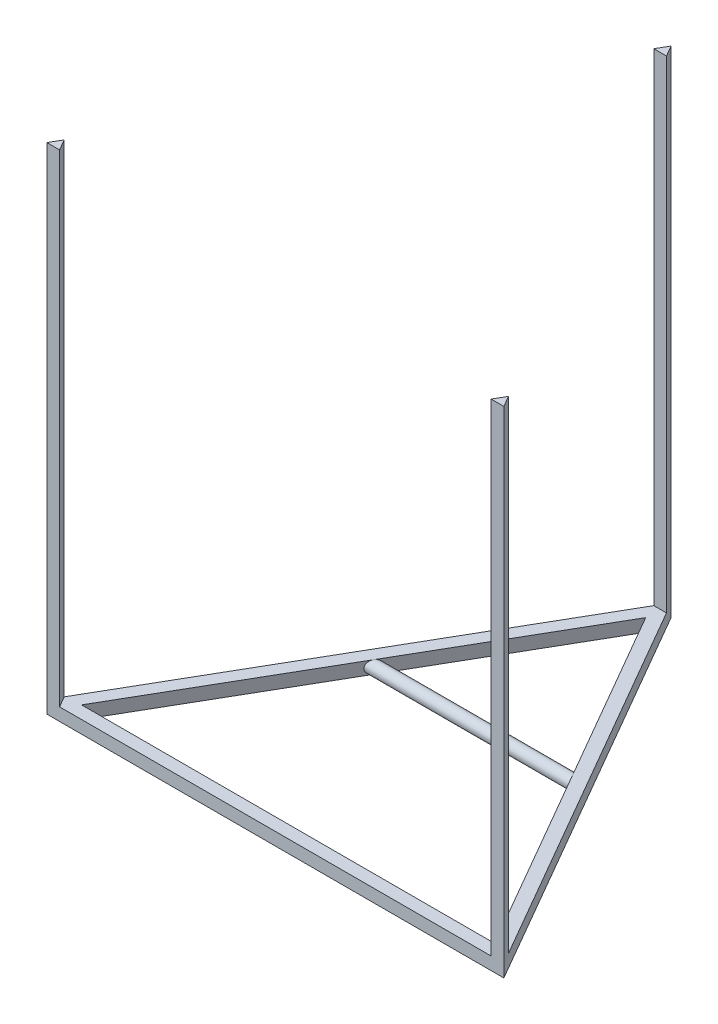
SolidWorks part; units mm, degrees
ref_plane "前视基准面" through (0, 0, 0) normal (0, 0, 1) x (1, 0, 0)
ref_plane "上视基准面" through (0, 0, 0) normal (0, 1, 0) x (1, 0, 0)
ref_plane "右视基准面" through (0, 0, 0) normal (1, 0, 0) x (0, 0, -1)
sketch "草图1" plane through (0, 0, 0) normal (0, 1, 0) x (1, 0, 0)
  line L0 (0, 0) -> (360, 0)
  line L1 (0, 0) -> (180, 311.7691)
  line L2 (180, 311.7691) -> (360, 0)
  dimension "D1" = 360
  dimension "D2" = 60
  dimension "D3" = 60
extrude "凸台-拉伸1" add sketch "草图1" along normal blind 10
sketch "草图2" plane through (0, 10, 0) normal (0, 1, 0) x (1, 0, 0)
  line L0 (360, 0) -> (355, 8.6603)
  line L1 (0, 0) -> (360, 0) construction
  line L2 (360, 0) -> (180, 311.7691) construction
  line L3 (355, 8.6603) -> (350, 0)
  line L4 (350, 0) -> (360, 0)
  line L5 (0, 0) -> (5, 8.6603)
  line L6 (180, 311.7691) -> (0, 0) construction
  line L7 (5, 8.6603) -> (10, 0)
  line L8 (10, 0) -> (0, 0)
  line L9 (180, 311.7691) -> (175, 303.1089)
  line L10 (175, 303.1089) -> (185, 303.1089)
  line L11 (185, 303.1089) -> (180, 311.7691)
  dimension "D1" = 10
  dimension "D2" = 10
  dimension "D3" = 10
  dimension "D4" = 10
  dimension "D5" = 10
extrude "凸台-拉伸2" add sketch "草图2" along normal blind 380
sketch "草图4" plane through (0, 0, 0) normal (0, -1, 0) x (-1, 0, 0)
  line L0 (-180, 291.7691) -> (-342.6795, 10)
  line L1 (-342.6795, 10) -> (-17.3205, 10)
  line L2 (-17.3205, 10) -> (-180, 291.7691)
  line L3 (-98.6603, 150.8846) -> (-90, 155.8846)
  line L4 (-180, 311.7691) -> (0, 0) construction
  line L5 (-180, 10) -> (-180, 0)
  line L6 (0, 0) -> (-360, 0) construction
  line L7 (-261.3397, 150.8846) -> (-270, 155.8846)
  line L8 (-360, 0) -> (-180, 311.7691) construction
  dimension "D1" = 10
  dimension "D2" = 10
  dimension "D3" = 10
  dimension "D4" = 90
  dimension "D5" = 90
  dimension "D6" = 90
extrude "切除-拉伸1" cut sketch "草图4" against normal blind 10 contours L0 L1 L2
ref_plane "基准面2" through (180, 0, 0) normal (-1, 0, 0) x (0, 0, 1)
sketch "草图5" plane through (180, 0, 0) normal (-1, 0, 0) x (0, 0, 1)
  line L0 (0, 0) -> (-156, 0)
  line L2 (-156, 0) -> (-156, 5)
  circle A0 centre (-156, 5) radius 5
  dimension "D1" = 156
  dimension "D2" = 5
extrude "凸台-拉伸3" add sketch "草图5" along normal blind 85 and the other way blind 85 contours A0
sketch "草图6" plane through (0, 0, 0) normal (0, -1, 0) x (-1, 0, 0)
  line L0 (-180, 291.7691) -> (-180, 311.7691)
